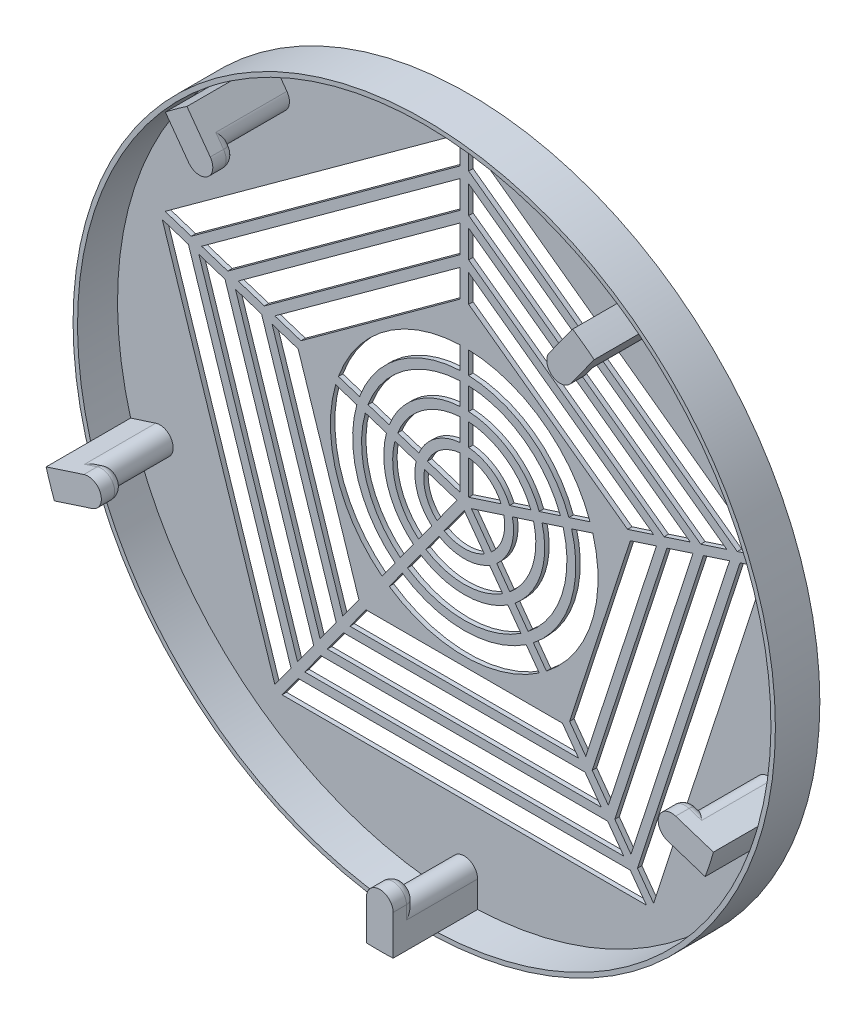
SolidWorks part; units mm, degrees
ref_plane "Front Plane" through (0, 0, 0) normal (0, 0, 1) x (1, 0, 0)
ref_plane "Top Plane" through (0, 0, 0) normal (0, 1, 0) x (1, 0, 0)
ref_plane "Right Plane" through (0, 0, 0) normal (1, 0, 0) x (0, 0, -1)
sketch "Sketch4" plane through (0, 0, 0) normal (0, 0, 1) x (1, 0, 0)
  circle A0 centre (0, 0) radius 79
  dimension "D1" = 158
extrude "Boss-Extrude2" add sketch "Sketch4" along normal blind 10
shell "Shell3" thickness 1 removed face at (79, 0, 10)
sketch "Sketch5" plane through (0, 0, 1) normal (0, 0, 1) x (1, 0, 0)
  line L0 (-1, 71.0931) -> (-67.3046, 22.92)
  line L6 (-67.9226, 21.0179) -> (-42.5965, -56.9278)
  line L7 (-40.9785, -58.1033) -> (40.9785, -58.1033)
  line L8 (42.5965, -56.9278) -> (67.9226, 21.0179)
  line L9 (67.3046, 22.92) -> (1, 71.0931)
  line L10 (0, 0) -> (0, 46.1033) construction
  line L11 (-1, 64.9128) -> (-61.4267, 21.0102)
  line L12 (-62.0447, 19.1081) -> (-38.9638, -51.9278)
  line L13 (-37.3458, -53.1033) -> (37.3458, -53.1033)
  line L14 (38.9638, -51.9278) -> (62.0447, 19.1081)
  line L15 (61.4267, 21.0102) -> (1, 64.9128)
  line L16 (-1, 62.4406) -> (-59.0756, 20.2463)
  line L17 (-59.6936, 18.3442) -> (-37.5107, -49.9278)
  line L18 (-35.8927, -51.1033) -> (35.8927, -51.1033)
  line L19 (37.5107, -49.9278) -> (59.6936, 18.3442)
  line L20 (59.0756, 20.2463) -> (1, 62.4406)
  line L21 (1, 0) -> (1, 1.3764)
  line L22 (-1, 0) -> (-1, 1.3764)
  line L23 (0.309, -0.9511) -> (1.618, -0.5257)
  line L24 (-0.309, 0.9511) -> (1, 1.3764)
  line L25 (-0.809, -0.5878) -> (0, -1.7013)
  line L26 (0.809, 0.5878) -> (1.618, -0.5257)
  line L27 (-0.809, 0.5878) -> (-1.618, -0.5257)
  line L28 (0.809, -0.5878) -> (0, -1.7013)
  line L29 (0.309, 0.9511) -> (-1, 1.3764)
  line L30 (-0.309, -0.9511) -> (-1.618, -0.5257)
  line L31 (-1, 0) -> (-1, 79) construction
  line L32 (0, 0) -> (0, 79) construction
  line L33 (1, 0) -> (1, 79) construction
  line L34 (-38.9638, -51.9278) -> (-42.5965, -56.9278)
  line L35 (-37.3458, -53.1033) -> (-40.9785, -58.1033)
  line L36 (37.3458, -53.1033) -> (40.9785, -58.1033)
  line L37 (38.9638, -51.9278) -> (42.5965, -56.9278)
  line L38 (62.0447, 19.1081) -> (67.9226, 21.0179)
  line L39 (61.4267, 21.0102) -> (67.3046, 22.92)
  line L40 (1, 64.9128) -> (1, 71.0931)
  line L41 (-1, 64.9128) -> (-1, 71.0931)
  line L42 (-62.0447, 19.1081) -> (-67.9226, 21.0179)
  line L43 (-61.4267, 21.0102) -> (-67.3046, 22.92)
  line L44 (-53.8157, 16.4343) -> (-59.6936, 18.3442)
  line L45 (-1, 56.2603) -> (-53.1977, 18.3364)
  line L46 (-53.8157, 16.4343) -> (-33.878, -44.9278)
  line L47 (-32.26, -46.1033) -> (32.26, -46.1033)
  line L48 (33.878, -44.9278) -> (53.8157, 16.4343)
  line L49 (53.1977, 18.3364) -> (1, 56.2603)
  line L50 (-53.1977, 18.3364) -> (-59.0756, 20.2463)
  line L51 (0, 63.1672) -> (0, 71.8197) construction
  line L52 (1, 56.2603) -> (1, 62.4406)
  line L53 (-1, 56.2603) -> (-1, 62.4406)
  line L54 (53.1977, 18.3364) -> (59.0756, 20.2463)
  line L55 (53.8157, 16.4343) -> (59.6936, 18.3442)
  line L56 (33.878, -44.9278) -> (37.5107, -49.9278)
  line L57 (32.26, -46.1033) -> (35.8927, -51.1033)
  line L58 (-33.878, -44.9278) -> (-37.5107, -49.9278)
  line L59 (-32.26, -46.1033) -> (-35.8927, -51.1033)
  circle A2 centre (0, 0) radius 46.1033 construction
  circle A3 centre (0, 0) radius 53.1033 construction
  circle A4 centre (0, 0) radius 51.1033 construction
  point P45 (0, 0)
  dimension "D3" = 2
  dimension "D2" = 5
  dimension "D1" = 58.1033
  dimension "D7" = 5
  dimension "D4" = 1
  dimension "D5" = 1
  dimension "D6" = 5
extrude "Cut-Extrude1" cut sketch "Sketch5" against normal blind 10 contours L12 L42 L6 L34 | L58 L46 L44 L17 | L47 L59 L18 L57 | L48 L56 L19 L55 | L36 L13 L35 L7 | L40 L15 L39 L9 | L49 L54 L20 L52 | L43 L11 L41 L0 | L45 L53 L16 L50 | L14 L38 L8 L37 region at (-32.7055, 45.0153, 1) region at (-52.9187, -17.1943, 1) region at (0, -55.642, 1) region at (32.7055, 45.0153, 1) region at (-28.5944, 39.3569, 1) region at (-46.2668, -15.033, 1) region at (0, -48.6477, 1) region at (46.2668, -15.033, 1) region at (28.5944, 39.3569, 1)
sketch "Sketch6" plane through (0, 0, 1) normal (0, 0, 1) x (1, 0, 0)
  line L0 (-1, 56.2603) -> (-53.1977, 18.3364) construction
  line L1 (-1, 53.7882) -> (-50.8466, 17.5725)
  line L2 (-51.4646, 15.6704) -> (-32.4249, -42.9278)
  line L3 (-30.8069, -44.1033) -> (30.8069, -44.1033)
  line L4 (32.4249, -42.9278) -> (51.4646, 15.6704)
  line L5 (50.8466, 17.5725) -> (1, 53.7882)
  line L6 (-1, 47.6078) -> (-44.9687, 15.6627)
  line L7 (-45.5868, 13.7606) -> (-28.7922, -37.9278)
  line L8 (-27.1742, -39.1033) -> (27.1742, -39.1033)
  line L9 (28.7922, -37.9278) -> (45.5868, 13.7606)
  line L10 (44.9687, 15.6627) -> (1, 47.6078)
  line L25 (-44.9687, 15.6627) -> (-50.8466, 17.5725)
  line L26 (-1, 45.1357) -> (-42.6176, 14.8988)
  line L27 (-43.2356, 12.9966) -> (-27.3391, -35.9278)
  line L28 (-25.7211, -37.1033) -> (25.7211, -37.1033)
  line L29 (27.3391, -35.9278) -> (43.2356, 12.9966)
  line L30 (42.6176, 14.8988) -> (1, 45.1357)
  line L32 (-37.3578, 11.0868) -> (-23.7064, -30.9278)
  line L33 (-22.0884, -32.1033) -> (22.0884, -32.1033)
  line L34 (23.7064, -30.9278) -> (37.3578, 11.0868)
  line L35 (36.7397, 12.9889) -> (1, 38.9554)
  line L36 (-45.5868, 13.7606) -> (-51.4646, 15.6704)
  line L37 (-36.7397, 12.9889) -> (-42.6176, 14.8988)
  line L38 (-37.3578, 11.0868) -> (-43.2356, 12.9966)
  line L39 (-1, 38.9554) -> (-1, 45.1357)
  line L40 (-1, 38.9554) -> (-36.7397, 12.9889)
  line L41 (0, 39.6819) -> (-0.8078, 39.095) [skipped]
  line L42 (1, 38.9554) -> (1, 45.1357)
  line L43 (1, 47.6078) -> (1, 53.7882)
  line L44 (-1, 47.6078) -> (-1, 53.7882)
  line L45 (44.9687, 15.6627) -> (50.8466, 17.5725)
  line L46 (45.5868, 13.7606) -> (51.4646, 15.6704)
  line L47 (36.7397, 12.9889) -> (42.6176, 14.8988)
  line L48 (37.3578, 11.0868) -> (43.2356, 12.9966)
  line L49 (23.7064, -30.9278) -> (27.3391, -35.9278)
  line L50 (22.0884, -32.1033) -> (25.7211, -37.1033)
  line L51 (27.1742, -39.1033) -> (30.8069, -44.1033)
  line L52 (28.7922, -37.9278) -> (32.4249, -42.9278)
  line L53 (-28.7922, -37.9278) -> (-32.4249, -42.9278)
  line L54 (-27.1742, -39.1033) -> (-30.8069, -44.1033)
  line L55 (-23.7064, -30.9278) -> (-27.3391, -35.9278)
  line L56 (-22.0884, -32.1033) -> (-25.7211, -37.1033)
  line L61 (0, 32.1033) -> (0, 48.3344) construction
  circle A0 centre (0, 0) radius 44.1033 construction
  circle A1 centre (0, 0) radius 39.1033 construction
  circle A2 centre (0, 0) radius 37.1033 construction
  circle A3 centre (0, 0) radius 32.1033 construction
  point P38 (0, 0)
  dimension "D1" = 5
  dimension "D2" = 2
  dimension "D6" = 2
  dimension "D7" = 5
extrude "Cut-Extrude2" cut sketch "Sketch6" against normal blind 10 contours L7 L53 L2 L36 | L27 L55 L32 L38 | L1 L25 L6 L44 | L39 L26 L37 L40 | L5 L43 L10 L45 | L35 L42 L30 L47 | L4 L46 L9 L52 | L34 L48 L29 L49 | L8 L51 L3 L54 | L28 L50 L33 L56
sketch "Sketch7" plane through (0, 0, 1) normal (0, 0, 1) x (1, 0, 0)
  line L0 (-1, 38.9554) -> (-36.7397, 12.9889) construction
  line L14 (-24.1647, 6.8001) -> (-28.9232, 8.3462)
  line L15 (-23.5467, 8.7023) -> (-28.3051, 10.2484)
  line L16 (1, 25.0834) -> (1, 30.0867)
  line L17 (-1, 25.0834) -> (-1, 30.0867)
  line L18 (23.5467, 8.7023) -> (28.3051, 10.2484)
  line L19 (24.1647, 6.8001) -> (28.9232, 8.3462)
  line L20 (13.9346, -20.8807) -> (16.8755, -24.9284)
  line L21 (15.5527, -19.7051) -> (18.4935, -23.7529)
  line L22 (-15.5527, -19.7051) -> (-18.4935, -23.7529)
  line L23 (-13.9346, -20.8807) -> (-16.8755, -24.9284)
  line L24 (1, 18.0757) -> (1, 23.0817)
  line L26 (-1, 18.0757) -> (-1, 23.0817)
  line L27 (-16.882, 6.5368) -> (-21.643, 8.0837)
  line L28 (-17.5, 4.6346) -> (-22.261, 6.1816)
  line L29 (-11.4336, -14.0358) -> (-14.3761, -18.0857)
  line L30 (-9.8156, -15.2113) -> (-12.7581, -19.2613)
  line L31 (9.8156, -15.2113) -> (12.7581, -19.2613)
  line L32 (11.4336, -14.0358) -> (14.3761, -18.0857)
  line L33 (17.5, 4.6346) -> (22.261, 6.1816)
  line L34 (16.882, 6.5368) -> (21.643, 8.0837)
  circle A0 centre (0, 0) radius 32.1033 construction
  arc A1 (-28.9232, 8.3462) -> (-18.4935, -23.7529) centre (0, 0) ccw
  arc A2 (-24.1647, 6.8001) -> (-15.5527, -19.7051) centre (0, 0) ccw
  arc A3 (-22.261, 6.1816) -> (-14.3761, -18.0857) centre (0, 0) ccw
  arc A4 (-17.5, 4.6346) -> (-11.4336, -14.0358) centre (0, 0) ccw
  arc A5 (-1, 30.0867) -> (-28.3051, 10.2484) centre (0, 0) ccw
  arc A6 (-1, 25.0834) -> (-23.5467, 8.7023) centre (0, 0) ccw
  arc A7 (-1, 23.0817) -> (-21.643, 8.0837) centre (0, 0) ccw
  arc A8 (-1, 18.0757) -> (-16.882, 6.5368) centre (0, 0) ccw
  arc A9 (28.3051, 10.2484) -> (1, 30.0867) centre (0, 0) ccw
  arc A10 (23.5467, 8.7023) -> (1, 25.0834) centre (0, 0) ccw
  arc A11 (21.643, 8.0837) -> (1, 23.0817) centre (0, 0) ccw
  arc A12 (18.4935, -23.7529) -> (28.9232, 8.3462) centre (0, 0) ccw
  arc A13 (15.5527, -19.7051) -> (24.1647, 6.8001) centre (0, 0) ccw
  arc A14 (14.3761, -18.0857) -> (22.261, 6.1816) centre (0, 0) ccw
  arc A15 (-16.8755, -24.9284) -> (16.8755, -24.9284) centre (0, 0) ccw
  arc A16 (-13.9346, -20.8807) -> (13.9346, -20.8807) centre (0, 0) ccw
  arc A17 (-12.7581, -19.2613) -> (12.7581, -19.2613) centre (0, 0) ccw
  arc A18 (-9.8156, -15.2113) -> (9.8156, -15.2113) centre (0, 0) ccw
  arc A19 (11.4336, -14.0358) -> (17.5, 4.6346) centre (0, 0) ccw
  arc A20 (16.882, 6.5368) -> (1, 18.0757) centre (0, 0) ccw
  point P34 (0, 0)
  dimension "D1" = 2
  dimension "D2" = 5
  dimension "D3" = 2
  dimension "D4" = 5
extrude "Cut-Extrude3" cut sketch "Sketch7" against normal blind 10
sketch "Sketch9" plane through (0, 0, 1) normal (0, 0, 1) x (1, 0, 0)
  line L0 (0, 0) -> (0, 16.1033) construction
  line L1 (10.208, 4.3682) -> (14.9766, 5.9177)
  line L2 (-1, 1.3764) -> (-8.2964, 3.7471)
  line L3 (-10.208, 4.3682) -> (-14.9766, 5.9177)
  line L4 (-10.826, 2.4661) -> (-15.5946, 4.0155)
  line L5 (0, -1.7013) -> (4.5094, -7.908)
  line L6 (10.826, 2.4661) -> (15.5946, 4.0155)
  line L7 (-1.618, -0.5257) -> (-6.1274, -6.7324)
  line L8 (-7.3089, -8.3585) -> (-10.256, -12.4149)
  line L9 (-5.6908, -9.5341) -> (-8.638, -13.5905)
  line L11 (-1, 1.3764) -> (-1, 9.0482)
  line L12 (-1.618, -0.5257) -> (-8.9144, 1.845)
  line L13 (0, -1.7013) -> (-4.5094, -7.908)
  line L14 (1, 11.0582) -> (1, 16.0722)
  line L15 (-1, 11.0582) -> (-1, 16.0722)
  line L16 (1, 1.3764) -> (8.2964, 3.7471)
  line L17 (1, 1.3764) -> (1, 9.0482)
  line L18 (1.618, -0.5257) -> (6.1274, -6.7324)
  line L20 (1.618, -0.5257) -> (8.9144, 1.845)
  line L21 (5.6908, -9.5341) -> (8.638, -13.5905)
  line L22 (7.3089, -8.3585) -> (10.256, -12.4149)
  arc A0 (-1, 16.0722) -> (-14.9766, 5.9177) centre (0, 0) ccw
  arc A1 (-1, 11.0582) -> (-10.208, 4.3682) centre (0, 0) ccw
  arc A2 (-1, 9.0482) -> (-8.2964, 3.7471) centre (0, 0) ccw
  arc A4 (-1, 18.0757) -> (-16.882, 6.5368) centre (0, 0) ccw construction
  arc A5 (8.2964, 3.7471) -> (1, 9.0482) centre (0, 0) ccw
  arc A6 (10.208, 4.3682) -> (1, 11.0582) centre (0, 0) ccw
  arc A7 (14.9766, 5.9177) -> (1, 16.0722) centre (0, 0) ccw
  arc A8 (-15.5946, 4.0155) -> (-10.256, -12.4149) centre (0, 0) ccw
  arc A9 (-10.826, 2.4661) -> (-7.3089, -8.3585) centre (0, 0) ccw
  arc A10 (-8.9144, 1.845) -> (-6.1274, -6.7324) centre (0, 0) ccw
  arc A11 (-8.638, -13.5905) -> (8.638, -13.5905) centre (0, 0) ccw
  arc A12 (-5.6908, -9.5341) -> (5.6908, -9.5341) centre (0, 0) ccw
  arc A13 (-4.5094, -7.908) -> (4.5094, -7.908) centre (0, 0) ccw
  arc A14 (10.256, -12.4149) -> (15.5946, 4.0155) centre (0, 0) ccw
  arc A15 (7.3089, -8.3585) -> (10.826, 2.4661) centre (0, 0) ccw
  arc A16 (6.1274, -6.7324) -> (8.9144, 1.845) centre (0, 0) ccw
  point P31 (0, 0)
  dimension "D1" = 2
  dimension "D2" = 5
  dimension "D3" = 2
extrude "Cut-Extrude5" cut sketch "Sketch9" against normal blind 10
sketch "Sketch11" plane through (0, 0, 1) normal (0, 0, 1) x (1, 0, 0)
  line L0 (-3, -72) -> (-3, -77.9423)
  line L1 (0, 0) -> (55.2595, -17.9549) construction
  line L2 (3, -72) -> (3, -77.9423)
  line L3 (-69.4031, -19.3961) -> (-75.0546, -21.2323)
  line L4 (-67.549, -25.1024) -> (-73.2005, -26.9387)
  line L5 (-39.8935, 60.0126) -> (-43.3863, 64.82)
  line L6 (69.4031, -19.3961) -> (75.0546, -21.2323)
  line L7 (65.6229, -21.3222) -> (74.1824, -24.1033) construction
  line L8 (-44.7476, 56.4859) -> (-48.2404, 61.2933)
  line L9 (67.549, -25.1024) -> (73.2005, -26.9387)
  line L10 (44.7476, 56.4859) -> (48.2404, 61.2933)
  line L11 (39.8935, 60.0126) -> (43.3863, 64.82)
  circle A0 centre (0, 0) radius 78 construction
  arc A1 (73.2005, -26.9387) -> (75.0546, -21.2323) centre (0, 0) ccw
  arc A2 (69.4031, -19.3961) -> (67.549, -25.1024) centre (68.4761, -22.2492) ccw
  arc A3 (3, -72) -> (-3, -72) centre (0, -72) ccw
  arc A4 (-3, -77.9423) -> (3, -77.9423) centre (0, 0) ccw
  arc A5 (-67.549, -25.1024) -> (-69.4031, -19.3961) centre (-68.4761, -22.2492) ccw
  arc A6 (-75.0546, -21.2323) -> (-73.2005, -26.9387) centre (0, 0) ccw
  arc A7 (-44.7476, 56.4859) -> (-39.8935, 60.0126) centre (-42.3205, 58.2492) ccw
  arc A8 (-43.3863, 64.82) -> (-48.2404, 61.2933) centre (0, 0) ccw
  arc A9 (39.8935, 60.0126) -> (44.7476, 56.4859) centre (42.3205, 58.2492) ccw
  arc A10 (48.2404, 61.2933) -> (43.3863, 64.82) centre (0, 0) ccw
  point P36 (0, 0)
  dimension "D3" = 6
  dimension "D1" = 5
extrude "Boss-Extrude3" add sketch "Sketch11" along normal blind 14
sketch "Sketch12" plane through (0, 0, 15) normal (0, 0, 1) x (1, 0, 0)
  line L0 (0, 0) -> (74.1824, -24.1033) construction
  line L1 (64.7092, -24.1797) -> (73.2005, -26.9387)
  line L2 (66.5633, -18.4733) -> (75.0546, -21.2323)
  line L3 (-0.9271, -2.8532) -> (73.2554, -26.9565) construction
  line L4 (0.9271, 2.8532) -> (75.1095, -21.2502) construction
  line L5 (-3, -69.014) -> (-3, -77.9423)
  line L6 (3, -69.014) -> (3, -77.9423)
  line L7 (-66.5633, -18.4733) -> (-75.0546, -21.2323)
  line L8 (-64.7092, -24.1797) -> (-73.2005, -26.9387)
  line L9 (-38.1384, 57.5969) -> (-43.3863, 64.82)
  line L10 (-42.9925, 54.0702) -> (-48.2404, 61.2933)
  line L11 (42.9925, 54.0702) -> (48.2404, 61.2933)
  line L12 (38.1384, 57.5969) -> (43.3863, 64.82)
  arc A0 (73.2005, -26.9387) -> (75.0546, -21.2323) centre (0, 0) ccw
  arc A1 (66.5633, -18.4733) -> (64.7092, -24.1797) centre (65.6362, -21.3265) ccw
  arc A2 (3, -69.014) -> (-3, -69.014) centre (0, -69.014) ccw
  arc A3 (-3, -77.9423) -> (3, -77.9423) centre (0, 0) ccw
  arc A4 (-64.7092, -24.1797) -> (-66.5633, -18.4733) centre (-65.6362, -21.3265) ccw
  arc A5 (-75.0546, -21.2323) -> (-73.2005, -26.9387) centre (0, 0) ccw
  arc A6 (-42.9925, 54.0702) -> (-38.1384, 57.5969) centre (-40.5654, 55.8335) ccw
  arc A7 (-43.3863, 64.82) -> (-48.2404, 61.2933) centre (0, 0) ccw
  arc A8 (38.1384, 57.5969) -> (42.9925, 54.0702) centre (40.5654, 55.8335) ccw
  arc A9 (48.2404, 61.2933) -> (43.3863, 64.82) centre (0, 0) ccw
  point P36 (0, 0)
  dimension "D1" = 3
  dimension "D2" = 3
  dimension "D3" = 5
extrude "Boss-Extrude4" add sketch "Sketch12" along normal blind 5
fillet "Fillet1" radius 2 15 edges at (-43.87, 55.278, 15) (-38.8021, 53.4065, 15) (-39.0159, 58.8047, 15) (43.87, 55.278, 15) (38.8021, 53.4065, 15) (39.0159, 58.8047, 15) (66.1291, -24.641, 15) (62.7831, -20.3995, 15) (67.9832, -18.9347, 15) (3, -70.507, 15) (0, -66.014, 15) (-3, -70.507, 15) (-67.9832, -18.9347, 15) (-62.7831, -20.3995, 15) (-66.1291, -24.641, 15)
